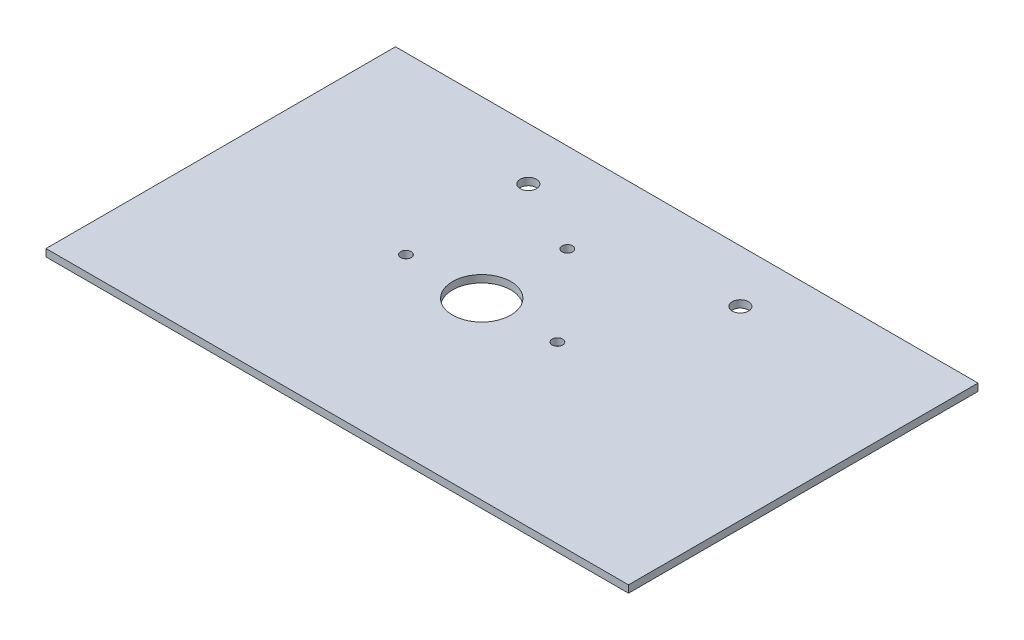
SolidWorks part; units mm, degrees
ref_plane "Front Plane" through (0, 0, 0) normal (0, 0, 1) x (1, 0, 0)
ref_plane "Top Plane" through (0, 0, 0) normal (0, 1, 0) x (1, 0, 0)
ref_plane "Right Plane" through (0, 0, 0) normal (1, 0, 0) x (0, 0, -1)
sketch "Sketch1" plane through (0, 0, 0) normal (0, 0, 1) x (1, 0, 0)
  line L0 (0, 0) -> (-254, 0)
  dimension "D1" = 254
base flange "Base-Flange1" sketch "Sketch1" end condition mid plane depth 152.4 reverse direction no thickness 3.175 reverse thickness direction no bend radius 1
sketch "Sketch6" plane through (0, 0, 0) normal (0, -1, 0) x (1, 0, 0)
  line L1 (0, 76.2) -> (-254, 76.2) construction
  line L2 (-254, 76.2) -> (-254, -76.2) construction
  circle A0 centre (-140.208, 0) radius 12.7
  dimension "D1" = 25.4
  dimension "D2" = 76.2
  dimension "D3" = 113.792
extrude "Cut-Extrude1" cut sketch "Sketch6" against normal through all normal cut yes
sketch "Sketch7" plane through (0, 0, 0) normal (0, -1, 0) x (1, 0, 0)
  line L0 (-140.208, -60.651) -> (-140.208, 60.651) construction
  circle A0 centre (-107.188, 0) radius 2.286
  circle A1 centre (-173.228, 0) radius 2.286
  point P7 (-140.208, 0)
  point P12 (-140.208, 0)
  dimension "D2" = 4.572
  dimension "D1" = 33.02
extrude "Cut-Extrude2" cut sketch "Sketch7" against normal through all normal cut yes
sketch "Sketch8" plane through (0, 0, 0) normal (0, -1, 0) x (1, 0, 0)
  line L0 (-29.228, 0) -> (-251.188, 0) construction
  circle A1 centre (-140.208, -37.338) radius 2.286
  point P2 (-140.208, 0)
  point P10 (-140.208, 0)
extrude "Cut-Extrude3" cut sketch "Sketch8" against normal through all normal cut yes
sketch "Sketch9" plane through (0, 3.175, 0) normal (0, 1, 0) x (1, 0, 0)
  line L0 (0, 76.2) -> (-254, 76.2) construction
  line L1 (-127, -76.2) -> (-127, 76.2) construction
  line L2 (0, -76.2) -> (-254, -76.2) construction
  circle A0 centre (-173.228, 53.34) radius 3.556
  circle A1 centre (-80.772, 53.34) radius 3.556
  point P2 (-173.228, 0)
  point P10 (-76.2, 76.2)
  point P11 (-127, 0)
  point P12 (-76.2, -76.2)
  dimension "D1" = 7.112
  dimension "D2" = 22.86
extrude "Cut-Extrude4" cut sketch "Sketch9" against normal through all normal cut yes
sketch "Bend-Lines1" [suppressed] plane through (0, 0, 0) normal (0, 1, 0) x (1, 0, 0)
sketch "Bounding-Box1" [suppressed] plane through (0, 0, 0) normal (0, 1, 0) x (1, 0, 0)
sheet metal parameters "Sheet-Metal1" thickness 3.175 parameters "D1"=1
flat pattern "Flat-Pattern1" [suppressed]
sketch "Bend-Lines2" plane through (0, 0, 0) normal (0, 1, 0) x (1, 0, 0)
sketch3d "Bounding-Box2" [suppressed]
  line L0 (152.4, 0, 0) -> (152.4, 152.4, 0) construction
  line L1 (0, 0, 0) -> (0, 152.4, 0) construction
  line L2 (152.4, 0, 0) -> (0, 0, 0) construction
  line L3 (152.4, 152.4, 0) -> (0, 152.4, 0) construction
sheet metal parameters "Sheet-Metal2" thickness 3.175 parameters "D1"=1
flat pattern "Flat-Pattern1"
sketch "Bend-Lines2" plane through (0, 0, 0) normal (0, 1, 0) x (1, 0, 0)
sketch3d "Bounding-Box2" [suppressed]
  line L0 (152.4, 0, 0) -> (152.4, 152.4, 0) construction
  line L1 (0, 0, 0) -> (0, 152.4, 0) construction
  line L2 (152.4, 0, 0) -> (0, 0, 0) construction
  line L3 (152.4, 152.4, 0) -> (0, 152.4, 0) construction
sheet metal parameters "Sheet-Metal3" thickness 3.175 parameters "D1"=1
flat pattern "Flat-Pattern1"
sketch "Bend-Lines2" plane through (0, 0, 0) normal (0, 1, 0) x (1, 0, 0)
sketch3d "Bounding-Box2" [suppressed]
  line L0 (152.4, 0, 0) -> (152.4, 152.4, 0) construction
  line L1 (0, 0, 0) -> (0, 152.4, 0) construction
  line L2 (152.4, 0, 0) -> (0, 0, 0) construction
  line L3 (152.4, 152.4, 0) -> (0, 152.4, 0) construction
sheet metal parameters "Sheet-Metal4" thickness 3.175 parameters "D1"=1
flat pattern "Flat-Pattern1"
sketch "Bend-Lines2" plane through (0, 0, 0) normal (0, 1, 0) x (1, 0, 0)
sketch3d "Bounding-Box2" [suppressed]
  line L0 (152.4, 0, 0) -> (152.4, 152.4, 0) construction
  line L1 (0, 0, 0) -> (0, 152.4, 0) construction
  line L2 (152.4, 0, 0) -> (0, 0, 0) construction
  line L3 (152.4, 152.4, 0) -> (0, 152.4, 0) construction
sheet metal parameters "Sheet-Metal5" thickness 3.175 parameters "D1"=1
flat pattern "Flat-Pattern1"
sketch "Bend-Lines2" plane through (0, 0, 0) normal (0, 1, 0) x (1, 0, 0)
sketch3d "Bounding-Box2" [suppressed]
  line L0 (254, 152.4, 0) -> (0, 152.4, 0) construction
  line L1 (254, 0, 0) -> (0, 0, 0) construction
  line L2 (254, 152.4, 0) -> (254, 0, 0) construction
  line L3 (0, 152.4, 0) -> (0, 0, 0) construction
